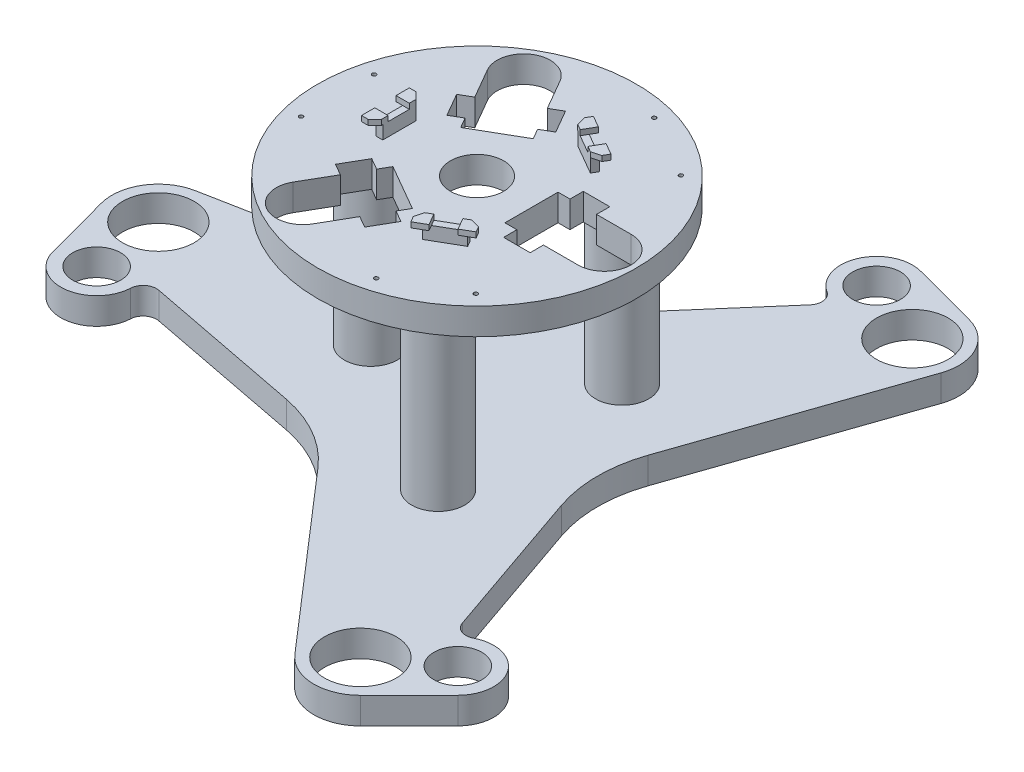
SolidWorks part; units mm, degrees
ref_plane "前视基准面" through (0, 0, 0) normal (0, 0, 1) x (1, 0, 0)
ref_plane "上视基准面" through (0, 0, 0) normal (0, 1, 0) x (1, 0, 0)
ref_plane "右视基准面" through (0, 0, 0) normal (1, 0, 0) x (0, 0, -1)
sketch "草图1" plane through (0, 0, 0) normal (0, 1, 0) x (1, 0, 0)
  circle A0 centre (0, 0) radius 120
  dimension "D1" = 240
extrude "凸台-拉伸1" add sketch "草图1" along normal blind 20
sketch "草图2" plane through (0, 20, 0) normal (0, 1, 0) x (1, 0, 0)
  circle A0 centre (60, 0) radius 15
  circle A1 centre (-30, -51.9615) radius 15
  circle A2 centre (-30, 51.9615) radius 15
  dimension "D1" = 30
  dimension "D2" = 60
  dimension "D3" = 3
extrude "切除-拉伸1" cut sketch "草图2" against normal through all both and the other way through all
ref_plane "基准面4" through (0, 10, 0) normal (0, 1, 0) x (1, 0, 0)
ref_axis "基准轴1" through (0, 0, 0) along (0, 1, 0)
sketch "草图3" plane through (0, 10, 0) normal (0, 1, 0) x (1, 0, 0)
  line L0 (0, 0) -> (200, 0) construction
  line L1 (0, 0) -> (100, -173.2051) construction
  line L2 (0, 0) -> (-100, -173.2051) construction
  line L3 (0, 0) -> (-200, 0) construction
  line L4 (0, 0) -> (-100, 173.2051) construction
  line L5 (0, 0) -> (100, 173.2051) construction
  line L6 (200, 0) -> (200, -115.4701) construction
  line L7 (200, -115.4701) -> (100, -173.2051) construction
  line L8 (100, -173.2051) -> (0, -230.9401) construction
  line L9 (0, -230.9401) -> (-100, -173.2051) construction
  line L10 (-100, -173.2051) -> (-200, -115.4701) construction
  line L11 (-200, -115.4701) -> (-200, 0) construction
  line L12 (-200, 0) -> (-200, 115.4701) construction
  line L13 (-200, 115.4701) -> (-100, 173.2051) construction
  line L14 (-100, 173.2051) -> (0, 230.9401) construction
  line L15 (0, 230.9401) -> (100, 173.2051) construction
  line L16 (100, 173.2051) -> (200, 115.4701) construction
  line L17 (200, 115.4701) -> (200, 0) construction
  dimension "D2" = 200
  dimension "D1" = 6
ref_axis "基准轴2" through (0, 0, 0) along (0, 1, 0)
sketch "草图6" plane through (0, 20, 0) normal (0, 1, 0) x (1, 0, 0)
  line L0 (41, 20) -> (41, -20)
  line L1 (41, -20) -> (50, -20)
  line L2 (41, 20) -> (50, 20)
  line L3 (0, 0) -> (200, 0) construction
  line L4 (50, 30) -> (50, 20)
  line L5 (50, 30) -> (70, 30)
  line L6 (70, 30) -> (70, 20)
  line L7 (70, 20) -> (96, 20)
  line L8 (50, -30) -> (70, -30)
  line L9 (70, -30) -> (70, -20)
  line L10 (50, -30) -> (50, -20)
  line L11 (70, -20) -> (96, -20)
  arc A0 (96, -20) -> (96, 20) centre (96, 0) ccw
  circle A2 centre (60, 0) radius 15 construction
  point P11 (60, 30)
  point P18 (60, -30)
  dimension "D5" = 20
  dimension "D1" = 40
  dimension "D2" = 20
  dimension "D3" = 19
  dimension "D4" = 55
  dimension "D6" = 20
  dimension "D7" = 0
  dimension "D8" = 30
  dimension "D9" = 20
  dimension "D10" = 0
  dimension "D11" = 30
extrude "切除-拉伸4" cut sketch "草图6" against normal through all both and the other way through all
pattern_circular "阵列(圆周)3" count 3 every 120 about axis through (0, 0, 0) along (0, 1, 0) of "切除-拉伸4"
sketch "草图7" plane through (0, 20, 0) normal (0, 1, 0) x (1, 0, 0)
  circle A0 centre (0, 0) radius 20
  dimension "D1" = 40
extrude "切除-拉伸5" cut sketch "草图7" against normal through all
sketch "草图8" plane through (0, 20, 0) normal (0, 1, 0) x (1, 0, 0)
  line L0 (0, 0) -> (-160.7766, 0) construction
  line L1 (-105, 27.5) -> (-105, -27.5) construction
  circle A0 centre (-105, 27.5) radius 1.5
  circle A1 centre (-105, -27.5) radius 1.5
  dimension "D4" = 3
  dimension "D5" = 3
  dimension "D1" = 55
  dimension "D2" = 27.5
  dimension "D3" = 105
extrude "切除-拉伸6" cut sketch "草图8" against normal through all both and the other way through all
sketch "草图9" plane through (0, 20, 0) normal (0, 1, 0) x (1, 0, 0)
  line L0 (-30, 10) -> (-30, -10)
  line L1 (-30, -10) -> (-35, -10)
  line L2 (-35, -10) -> (-35, 10)
  line L3 (-35, 10) -> (-30, 10)
  dimension "D1" = 20
  dimension "D2" = 5
  dimension "D3" = 30
  dimension "D4" = 10
extrude "凸台-拉伸2" [suppressed] add sketch "草图9" along normal blind 10
pattern_circular "阵列(圆周)4" count 3 every 120 about axis through (0, 0, 0) along (0, 1, 0) of "切除-拉伸6", "凸台-拉伸2" reverse direction yes
sketch "草图12" plane through (0, 20, 0) normal (0, 1, 0) x (1, 0, 0)
  line L0 (-64, 13) -> (-64, -12)
  line L1 (-64, -12) -> (-59, -12)
  line L2 (-59, -12) -> (-59, 13)
  line L3 (-59, 13) -> (-64, 13)
  dimension "D1" = 64
  dimension "D2" = 25
  dimension "D3" = 13
  dimension "D4" = 5
extrude "凸台-拉伸3" add sketch "草图12" along normal blind 10
sketch "草图13" plane through (0, 30, 0) normal (0, 1, 0) x (1, 0, 0)
  line L0 (-69, 8) -> (-59, 8)
  line L1 (-59, -13) -> (-59, -8)
  line L2 (-69, 8) -> (-69, 18)
  line L3 (-69, 18) -> (-64, 18)
  line L4 (-64, 18) -> (-59, 13)
  line L5 (-59, 13) -> (-59, 8)
  line L6 (-59, -12) -> (-59, 13) construction
  line L7 (0, 0) -> (-180.3971, 0) construction
  line L8 (-64, -18) -> (-59, -13)
  line L9 (-69, -18) -> (-64, -18)
  line L10 (-69, -8) -> (-69, -18)
  line L11 (-69, -8) -> (-59, -8)
  dimension "D1" = 8
  dimension "D2" = 10
  dimension "D3" = 10
  dimension "D4" = 5
extrude "凸台-拉伸4" add sketch "草图13" along normal blind 4
pattern_circular "阵列(圆周)5" count 3 every 120 about axis through (0, 0, 0) along (0, 1, 0) of "凸台-拉伸3", "凸台-拉伸4"
sketch "草图14" plane through (0, 0, 0) normal (0, -1, 0) x (1, 0, 0)
  circle A0 centre (-80, 0) radius 20
  circle A1 centre (40, 69.282) radius 20
  circle A2 centre (40, -69.282) radius 20
  dimension "D1" = 40
  dimension "D2" = 80
  dimension "D3" = 3
extrude "凸台-拉伸5" add sketch "草图14" along normal blind 130
sketch "草图15" plane through (0, 10, -10) normal (0, -1, 0) x (1, 0, 0)
  line L0 (-267, 10) -> (265, 10) construction
  line L1 (133.5, 241.2288) -> (-133.5, -221.2288) construction
  line L2 (-133.5, 241.2288) -> (133.5, -221.2288) construction
  circle A0 centre (0, 10) radius 240
  circle A1 centre (120, 217.8461) radius 27
  circle A2 centre (-120, 217.8461) radius 27
  circle A4 centre (120, -197.8461) radius 27
  circle A5 centre (-120, -197.8461) radius 27
  circle A6 centre (-240, 10) radius 27
  circle A7 centre (240, 10) radius 27
  circle A8 centre (0, 10) radius 275
  circle A9 centre (0, 10) radius 205
  circle A10 centre (234.2578, -42.185) radius 18
  point P9 (120, 217.8461)
  point P10 (240, 10)
  point P11 (-120, 217.8461)
  point P12 (-240, 10)
  point P13 (-120, -197.8461)
  point P14 (120, -197.8461)
  dimension "D1" = 480
  dimension "D4" = 54
  dimension "D5" = 54
  dimension "D6" = 550
  dimension "D7" = 54
  dimension "D8" = 54
  dimension "D9" = 54
  dimension "D10" = 54
  dimension "D11" = 410
  dimension "D12" = 52.5
  dimension "D13" = 36
  dimension "D2" = 60
  dimension "D3" = 60
sketch "草图16" plane through (0, -130, 0) normal (0, -1, 0) x (1, 0, 0)
  line L0 (-133.5, 231.2288) -> (133.5, -231.2288) construction
  line L1 (133.5, 231.2288) -> (-133.5, -231.2288) construction
  line L2 (-267, 0) -> (265, 0) construction
  line L3 (-246.6557, 34.3613) -> (-240.9352, 35.4694) construction
  line L4 (-246.6285, -34.3666) -> (-76.5344, -67.1738)
  line L5 (-19.7617, 100.0353) -> (93.5519, 230.7699)
  line L6 (153.0766, 196.4033) -> (151.1783, 190.916) construction
  line L7 (-19.9071, -99.8676) -> (59.3884, -191.3541)
  line L8 (96.4882, -32.4094) -> (153.0856, -196.4294)
  line L9 (-260.3324, 59.1933) -> (-273.8004, 9.0848)
  line L11 (181.4291, 195.8578) -> (144.7678, 232.5757)
  line L13 (78.9033, -255.0511) -> (129.0326, -241.6605)
  line L15 (136.0233, 147.1089) -> (96.514, 32.9035)
  line L16 (89.749, -226.3823) -> (93.5519, -230.7699) construction
  line L17 (-195.4061, 44.2882) -> (-76.3114, 67.3565)
  circle A0 centre (-240, 0) radius 27
  circle A1 centre (120, 207.8461) radius 27
  circle A2 centre (120, -207.8461) radius 27
  circle A3 centre (0, 0) radius 275 construction
  arc A4 (-273.8004, 9.0848) -> (-246.6285, -34.3666) centre (-240, 0) ccw
  arc A5 (93.5519, -230.7699) -> (96.2551, -233.5595) centre (120, -207.8461) ccw construction
  arc A6 (144.7678, 232.5757) -> (93.5519, 230.7699) centre (120, 207.8461) ccw
  circle A7 centre (40, 69.282) radius 20.2277 construction
  circle A8 centre (40, -69.282) radius 20 construction
  circle A9 centre (-80, 0) radius 20 construction
  arc A10 (-76.5344, -67.1738) -> (-19.9071, -99.8676) centre (-95.473, -165.3641) cw
  arc A11 (96.4882, -32.4094) -> (96.514, 32.9035) centre (191.0186, 0.2097) cw
  arc A12 (-76.3114, 67.3565) -> (-19.7617, 100.0353) centre (-95.3277, 165.5318) ccw
  circle A13 centre (71.9353, -228.9657) radius 18
  circle A14 centre (0, 0) radius 240 construction
  arc A15 (57.2652, -206.2989) -> (78.9033, -255.0511) centre (71.9353, -228.9657) ccw
  arc A16 (-207.2942, 53.5866) -> (-260.3324, 59.1933) centre (-234.2578, 52.185) ccw
  circle A17 centre (-234.2578, 52.185) radius 18
  arc A18 (150.0274, 152.7426) -> (181.4291, 195.8578) centre (162.3225, 176.7807) ccw
  circle A19 centre (162.3225, 176.7807) radius 18
  arc A20 (129.0326, -241.6605) -> (153.0856, -196.4294) centre (120, -207.8461) ccw
  arc A21 (-207.2942, 53.5866) -> (-195.4061, 44.2882) centre (-197.3077, 54.1058) ccw
  arc A22 (136.0233, 147.1089) -> (150.0274, 152.7426) centre (145.4737, 143.8395) cw
  arc A23 (57.2652, -206.2989) -> (59.3884, -191.3541) centre (51.8318, -197.9037) ccw
  point P11 (-75, 129.9038)
  point P12 (-75, -129.9038)
  point P15 (150, 0)
  point P18 (-275, 0)
  point P22 (137.5, 238.157)
  point P25 (137.5, -238.157)
  dimension "D1" = 54
  dimension "D5" = 40
  dimension "D6" = 40
  dimension "D7" = 40.4554
  dimension "D8" = 35
  dimension "D9" = 100
  dimension "D10" = 52.5
  dimension "D11" = 36
  dimension "D12" = 52.5
  dimension "D13" = 36
  dimension "D14" = 52.5
  dimension "D15" = 36
  dimension "D16" = 54
  dimension "D17" = 54
  dimension "D18" = 54
  dimension "D19" = 10
  dimension "D20" = 10
  dimension "D21" = 10
  dimension "D2" = 150
  dimension "D3" = 150
  dimension "D4" = 150
extrude "凸台-拉伸6" add sketch "草图16" along normal blind 20 separate body
